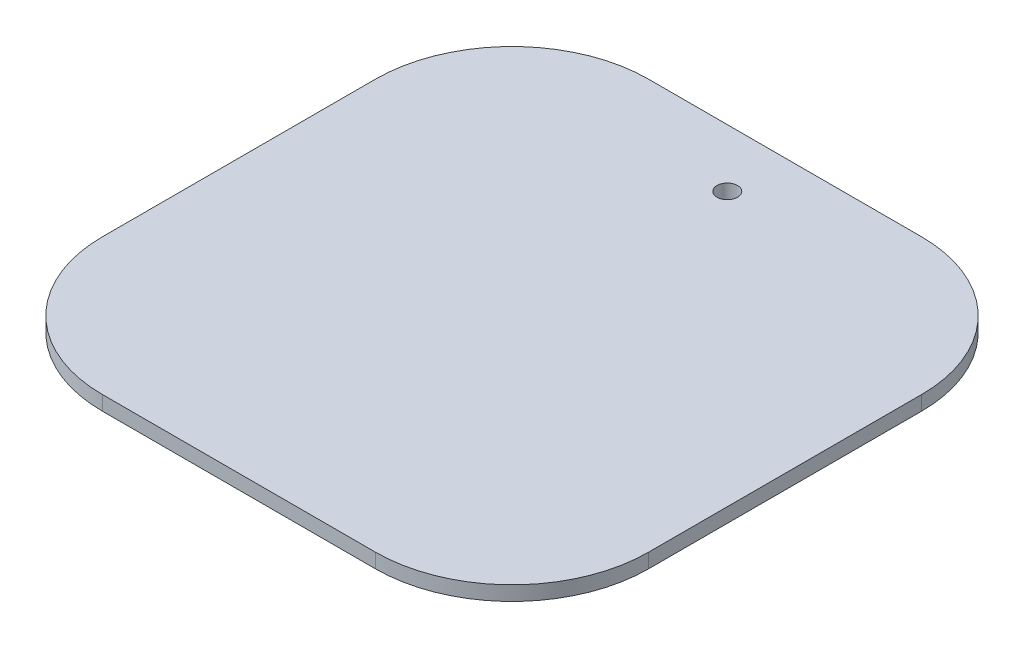
SolidWorks part; units mm, degrees
ref_plane "Front" through (0, 0, 0) normal (0, 0, 1) x (1, 0, 0)
ref_plane "Top" through (0, 0, 0) normal (0, 1, 0) x (1, 0, 0)
ref_plane "Right" through (0, 0, 0) normal (1, 0, 0) x (0, 0, -1)
sketch "Sketch1" plane through (0, 0, 0) normal (0, 1, 0) x (1, 0, 0)
  line L1 (-30, 60) -> (30, 60)
  line L2 (-60, 30) -> (-60, -30)
  line L3 (-30, -60) -> (30, -60)
  line L4 (60, 30) -> (60, -30)
  line L5 (-60, 60) -> (60, -60) construction
  line L6 (-60, -60) -> (60, 60) construction
  arc A0 (30, -60) -> (60, -30) centre (30, -30) ccw
  arc A1 (60, 30) -> (30, 60) centre (30, 30) ccw
  arc A2 (-30, 60) -> (-60, 30) centre (-30, 30) ccw
  arc A3 (-60, -30) -> (-30, -60) centre (-30, -30) ccw
  point P0 (0, 0)
  dimension "D3" = 30
  dimension "D1" = 120
  dimension "D2" = 120
extrude "Boss-Extrude1" add sketch "Sketch1" along normal blind 3.175
hole_wizard "M4 Clearance Hole1" positions "Sketch2" profile "Sketch3" hole size "M4" standard "ANSI Metric"
sketch "Sketch2" plane through (0, 3.175, 0) normal (0, 1, 0) x (1, 0, 0)
  line L0 (0, 60) -> (0, 47.3)
  line L1 (30, 60) -> (-30, 60) construction
  point P0 (0, 47.3)
  dimension "D1" = 12.7
sketch "Sketch3" plane through (0, 3.175, -47.3) normal (1, 0, 0) x (0, 0, 1)
  line L0 (0, 0) -> (0, 51.3519)
  line L1 (0, 51.3519) -> (2.25, 50)
  line L2 (2.25, 50) -> (2.25, 0)
  line L5 (2.25, 0) -> (0, 0)
  line L10 (0, 51.3519) -> (-2.25, 50) construction
  line L11 (0, -6.35) -> (0, 107.95) construction
  dimension "Hole Dia." = 4.5
  dimension "Hole Depth" = 50
  dimension "Drill Angle" = 118
